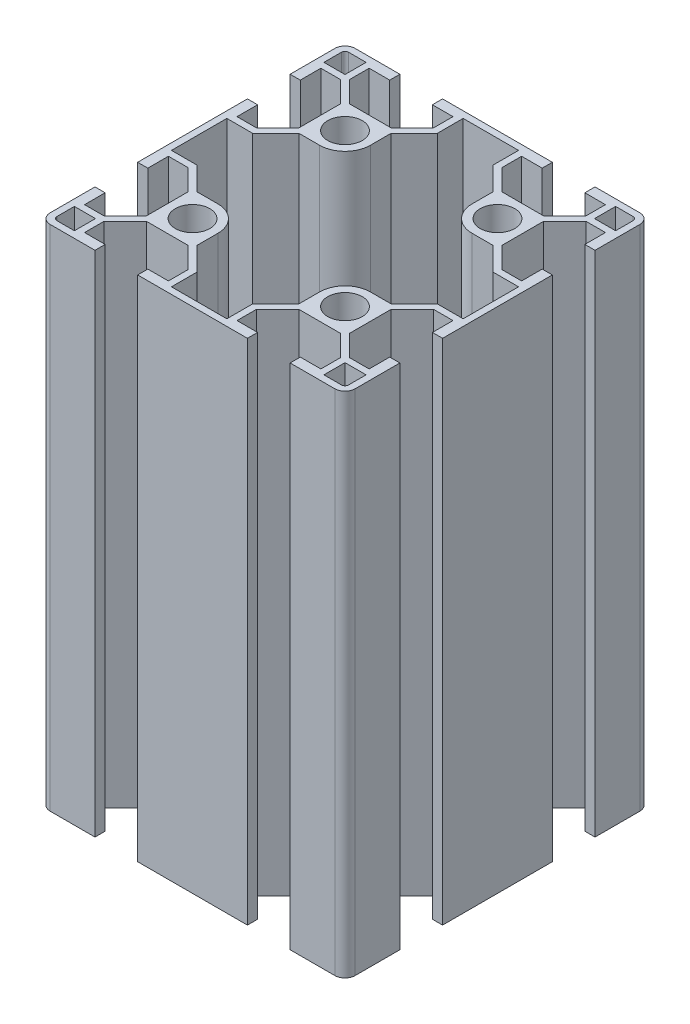
SolidWorks part; units mm, degrees
ref_plane "前视基准面" through (0, 0, 0) normal (0, 0, 1) x (1, 0, 0)
ref_plane "上视基准面" through (0, 0, 0) normal (0, 1, 0) x (1, 0, 0)
ref_plane "右视基准面" through (0, 0, 0) normal (1, 0, 0) x (0, 0, -1)
other "Configuration Table"
sketch "草图1" plane through (0, 0, 0) normal (0, 1, 0) x (1, 0, 0)
  line L0 (-80.888, 0) -> (79.2123, 0) construction
  line L1 (0, 66.3403) -> (0, -67.7113) construction
  line L2 (0, 0) -> (-70.1525, 70.1525) construction
  line L3 (-30, 30) -> (-19.2, 30)
  line L4 (-19.2, 30) -> (-19.2, 28)
  line L5 (-19.2, 28) -> (-23.25, 28)
  line L6 (-23.25, 28) -> (-23.25, 24.1692)
  line L7 (-23.25, 24.1692) -> (-19.0808, 20)
  line L8 (-19.0808, 20) -> (-10.9192, 20)
  line L9 (-10.9192, 20) -> (-6.75, 24.1692)
  line L10 (-6.75, 24.1692) -> (-6.75, 28)
  line L11 (-6.75, 28) -> (-10.8, 28)
  line L12 (-10.8, 28) -> (-10.8, 30)
  line L13 (-10.8, 30) -> (10.8, 30)
  line L14 (-5.45, 28) -> (-5.45, 28.7)
  line L15 (-5.45, 28) -> (-5.45, 23.6308)
  line L16 (-5.45, 23.6308) -> (-10, 19.0808)
  line L17 (-10, 19.0808) -> (-10, 10)
  line L18 (-5.45, 28.7) -> (5.45, 28.7)
  line L19 (-28.7, 28.7) -> (-24.55, 28.7)
  line L20 (-24.55, 28.7) -> (-24.55, 24.55)
  line L21 (-10.9192, 20) -> (-10, 19.0808) construction
  line L22 (-20, 10.9192) -> (-19.0808, 10) construction
  line L23 (-28.7, 24.55) -> (-24.55, 24.55)
  line L24 (-28.7, 28.7) -> (-28.7, 24.55)
  line L25 (-28.7, 5.45) -> (-28.7, -5.45)
  line L26 (-19.0808, 10) -> (-10, 10)
  line L27 (-23.6308, 5.45) -> (-19.0808, 10)
  line L28 (-28, 5.45) -> (-23.6308, 5.45)
  line L29 (-28, 5.45) -> (-28.7, 5.45)
  line L30 (-30, 10.8) -> (-30, -10.8)
  line L31 (-28, 10.8) -> (-30, 10.8)
  line L32 (-28, 6.75) -> (-28, 10.8)
  line L33 (-24.1692, 6.75) -> (-28, 6.75)
  line L34 (-20, 10.9192) -> (-24.1692, 6.75)
  line L35 (-20, 19.0808) -> (-20, 10.9192)
  line L36 (-24.1692, 23.25) -> (-20, 19.0808)
  line L37 (-28, 23.25) -> (-24.1692, 23.25)
  line L38 (-28, 19.2) -> (-28, 23.25)
  line L39 (-30, 19.2) -> (-28, 19.2)
  line L40 (-30, 30) -> (-30, 19.2)
  line L41 (20, 10.9192) -> (19.0808, 10) construction
  line L42 (10.9192, 20) -> (10, 19.0808) construction
  line L43 (0, 0) -> (70.1525, 70.1525) construction
  line L44 (30, 30) -> (30, 19.2)
  line L45 (30, 19.2) -> (28, 19.2)
  line L46 (28, 19.2) -> (28, 23.25)
  line L47 (28, 23.25) -> (24.1692, 23.25)
  line L48 (24.1692, 23.25) -> (20, 19.0808)
  line L49 (20, 19.0808) -> (20, 10.9192)
  line L50 (20, 10.9192) -> (24.1692, 6.75)
  line L51 (24.1692, 6.75) -> (28, 6.75)
  line L52 (28, 6.75) -> (28, 10.8)
  line L53 (28, 10.8) -> (30, 10.8)
  line L54 (30, 10.8) -> (30, -10.8)
  line L55 (28, 5.45) -> (28.7, 5.45)
  line L56 (28, 5.45) -> (23.6308, 5.45)
  line L57 (23.6308, 5.45) -> (19.0808, 10)
  line L58 (19.0808, 10) -> (10, 10)
  line L59 (28.7, 5.45) -> (28.7, -5.45)
  line L60 (28.7, 28.7) -> (28.7, 24.55)
  line L61 (28.7, 24.55) -> (24.55, 24.55)
  line L62 (24.55, 28.7) -> (24.55, 24.55)
  line L63 (28.7, 28.7) -> (24.55, 28.7)
  line L64 (10, 19.0808) -> (10, 10)
  line L65 (5.45, 23.6308) -> (10, 19.0808)
  line L66 (5.45, 28) -> (5.45, 23.6308)
  line L67 (5.45, 28) -> (5.45, 28.7)
  line L68 (10.8, 28) -> (10.8, 30)
  line L69 (6.75, 28) -> (10.8, 28)
  line L70 (6.75, 24.1692) -> (6.75, 28)
  line L71 (10.9192, 20) -> (6.75, 24.1692)
  line L72 (19.0808, 20) -> (10.9192, 20)
  line L73 (23.25, 24.1692) -> (19.0808, 20)
  line L74 (23.25, 28) -> (23.25, 24.1692)
  line L75 (19.2, 28) -> (23.25, 28)
  line L76 (19.2, 30) -> (19.2, 28)
  line L77 (30, 30) -> (19.2, 30)
  line L78 (0, 0) -> (70.1525, -70.1525) construction
  line L79 (10.9192, -20) -> (10, -19.0808) construction
  line L80 (20, -10.9192) -> (19.0808, -10) construction
  line L81 (-20, -10.9192) -> (-19.0808, -10) construction
  line L82 (-10.9192, -20) -> (-10, -19.0808) construction
  line L83 (0, 0) -> (-70.1525, -70.1525) construction
  line L84 (30, -30) -> (19.2, -30)
  line L85 (19.2, -30) -> (19.2, -28)
  line L86 (19.2, -28) -> (23.25, -28)
  line L87 (23.25, -28) -> (23.25, -24.1692)
  line L88 (23.25, -24.1692) -> (19.0808, -20)
  line L89 (19.0808, -20) -> (10.9192, -20)
  line L90 (10.9192, -20) -> (6.75, -24.1692)
  line L91 (6.75, -24.1692) -> (6.75, -28)
  line L92 (6.75, -28) -> (10.8, -28)
  line L93 (10.8, -28) -> (10.8, -30)
  line L94 (5.45, -28) -> (5.45, -28.7)
  line L95 (5.45, -28) -> (5.45, -23.6308)
  line L96 (5.45, -23.6308) -> (10, -19.0808)
  line L97 (10, -19.0808) -> (10, -10)
  line L98 (28.7, -28.7) -> (24.55, -28.7)
  line L99 (24.55, -28.7) -> (24.55, -24.55)
  line L100 (28.7, -24.55) -> (24.55, -24.55)
  line L101 (28.7, -28.7) -> (28.7, -24.55)
  line L102 (19.0808, -10) -> (10, -10)
  line L103 (23.6308, -5.45) -> (19.0808, -10)
  line L104 (28, -5.45) -> (23.6308, -5.45)
  line L105 (28, -5.45) -> (28.7, -5.45)
  line L106 (28, -10.8) -> (30, -10.8)
  line L107 (28, -6.75) -> (28, -10.8)
  line L108 (24.1692, -6.75) -> (28, -6.75)
  line L109 (20, -10.9192) -> (24.1692, -6.75)
  line L110 (20, -19.0808) -> (20, -10.9192)
  line L111 (24.1692, -23.25) -> (20, -19.0808)
  line L112 (28, -23.25) -> (24.1692, -23.25)
  line L113 (28, -19.2) -> (28, -23.25)
  line L114 (30, -19.2) -> (28, -19.2)
  line L115 (30, -30) -> (30, -19.2)
  line L116 (-30, -30) -> (-30, -19.2)
  line L117 (-30, -19.2) -> (-28, -19.2)
  line L118 (-28, -19.2) -> (-28, -23.25)
  line L119 (-28, -23.25) -> (-24.1692, -23.25)
  line L120 (-24.1692, -23.25) -> (-20, -19.0808)
  line L121 (-20, -19.0808) -> (-20, -10.9192)
  line L122 (-20, -10.9192) -> (-24.1692, -6.75)
  line L123 (-24.1692, -6.75) -> (-28, -6.75)
  line L124 (-28, -6.75) -> (-28, -10.8)
  line L125 (-28, -10.8) -> (-30, -10.8)
  line L126 (-28, -5.45) -> (-28.7, -5.45)
  line L127 (-28, -5.45) -> (-23.6308, -5.45)
  line L128 (-23.6308, -5.45) -> (-19.0808, -10)
  line L129 (-19.0808, -10) -> (-10, -10)
  line L130 (-28.7, -28.7) -> (-28.7, -24.55)
  line L131 (-28.7, -24.55) -> (-24.55, -24.55)
  line L132 (-24.55, -28.7) -> (-24.55, -24.55)
  line L133 (-28.7, -28.7) -> (-24.55, -28.7)
  line L134 (-5.45, -28.7) -> (5.45, -28.7)
  line L135 (-10, -19.0808) -> (-10, -10)
  line L136 (-5.45, -23.6308) -> (-10, -19.0808)
  line L137 (-5.45, -28) -> (-5.45, -23.6308)
  line L138 (-5.45, -28) -> (-5.45, -28.7)
  line L139 (-10.8, -30) -> (10.8, -30)
  line L140 (-10.8, -28) -> (-10.8, -30)
  line L141 (-6.75, -28) -> (-10.8, -28)
  line L142 (-6.75, -24.1692) -> (-6.75, -28)
  line L143 (-10.9192, -20) -> (-6.75, -24.1692)
  line L144 (-19.0808, -20) -> (-10.9192, -20)
  line L145 (-23.25, -24.1692) -> (-19.0808, -20)
  line L146 (-23.25, -28) -> (-23.25, -24.1692)
  line L147 (-19.2, -28) -> (-23.25, -28)
  line L148 (-19.2, -30) -> (-19.2, -28)
  line L149 (-30, -30) -> (-19.2, -30)
  circle A0 centre (-15, 15) radius 3.4
  circle A1 centre (15, 15) radius 3.4
  circle A2 centre (15, -15) radius 3.4
  circle A3 centre (-15, -15) radius 3.4
  point P75 (0, 28.7)
  point P78 (0, 30)
  point P119 (28.7, 0)
  point P122 (30, 0)
  point P140 (-30, 0)
  point P144 (-28.7, 0)
  point P160 (0, -30)
  point P161 (0, -28.7)
  point P162 (-52.8921, 9.9153)
  dimension "D14" = 6.8
  dimension "D2" = 30
  dimension "D3" = 8.4
  dimension "D4" = 10.8
  dimension "D5" = 2
  dimension "D6" = 2
  dimension "D7" = 16.5
  dimension "D8" = 1.3
  dimension "D9" = 1.3
  dimension "D10" = 4.05
  dimension "D11" = 1.3
  dimension "D12" = 10
  dimension "D13" = 1.3
  dimension "D15" = 1.3
  dimension "D16" = 1.3
  dimension "D17" = 15
extrude "凸台-拉伸1" add sketch "草图1" along normal blind 100 contours L137 L138 L134 L94 L95 L96 L97 L102 L103 L104 L105 L59 L55 L56 L57 L58 L64 L65 L66 L67 L18 L14 L15 L16 L17 L26 L27 L28 L29 L25 L126 L127 L128 L129 L135 L136 | A2 | A1 | A0 | A3 | L98 L101 L100 L99 | L60 L63 L62 L61 | L19 L24 L23 L20 | L130 L133 L132 L131 | L44 L45 L46 L47 L48 L49 L50 L51 L52 L53 L54 L106 L107 L108 L109 L110 L111 L112 L113 L114 L115 L84 L85 L86 L87 L88 L89 L90 L91 L92 L93 L139 L140 L141 L142 L143 L144 L145 L146 L147 L148 L149 L116 L117 L118 L119 L120 L121 L122 L123 L124 L125 L30 L31 L32 L33 L34 L35 L36 L37 L38 L39 L40 L3 L4 L5 L6 L7 L8 L9 L10 L11 L12 L13 L68 L69 L70 L71 L72 L73 L74 L75 L76 L77 region at (0, 0, 0) region at (-26.625, 0, -26.625) region at (26.625, 0, -26.625) region at (26.625, 0, 26.625) region at (-26.625, 0, 26.625) region at (-15, 0, -15) region at (15, 0, -15) region at (15, 0, 15) region at (-15, 0, 15)
fillet "圆角1" radius 0.7 4 edges at (-28.7, 50, 28.7) (-28.7, 50, -28.7) (28.7, 50, -28.7) (28.7, 50, 28.7)
fillet "圆角2" radius 2 4 edges at (30, 50, 30) (-30, 50, 30) (-30, 50, -30) (30, 50, -30)
fillet "圆角3" radius 5 4 edges at (10, 50, 10) (10, 50, -10) (-10, 50, -10) (-10, 50, 10)
